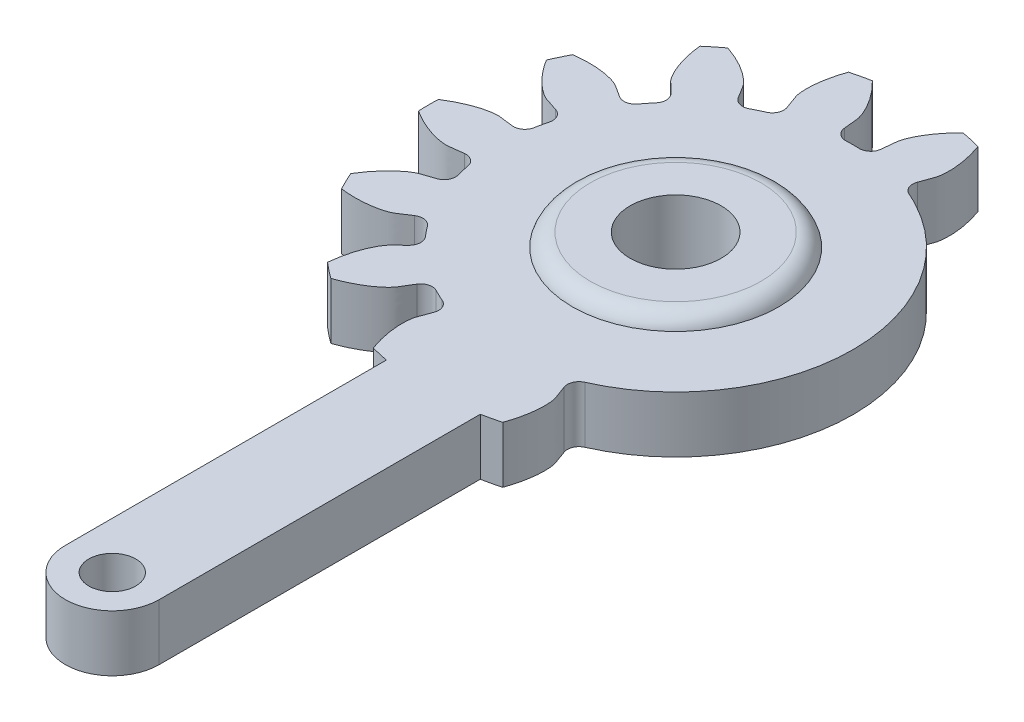
SolidWorks part; units mm, degrees
ref_plane "Front Plane" through (0, 0, 0) normal (0, 0, 1) x (1, 0, 0)
ref_plane "Top Plane" through (0, 0, 0) normal (0, 1, 0) x (1, 0, 0)
ref_plane "Right Plane" through (0, 0, 0) normal (1, 0, 0) x (0, 0, -1)
ref_plane "Plane1" through (0, 0, 0) normal (0, -1, 0) x (1, 0, 0)
sketch "Sketch1" plane through (0, 0, 0) normal (0, -1, 0) x (1, 0, 0)
  line L0 (9, 29) -> (9, 11.9029)
  line L1 (14, 11.9029) -> (14, 29)
  arc A0 (9, 11.9029) -> (14, 11.9029) centre (11.5, -1) ccw
  arc A1 (14, 29) -> (9, 29) centre (11.5, 29) ccw
extrude "Boss-Extrude1" add sketch "Sketch1" against normal blind 3
sketch "Sketch2" plane through (0, 3, 0) normal (0, 1, 0) x (-1, 0, 0)
  arc A0 (-8.2696, 7.8769) -> (-6.6141, 7.0847) centre (-11.5, -1) cw
  arc A1 (-3.7528, 9.6168) -> (-8.093, 11.6936) centre (-11.5, -1) ccw
  spline S0 degree 3 poles (-8.2696, 7.8769) (-8.0543, 8.4631) (-7.8019, 9.15) (-7.7905, 9.2032) (-7.7728, 9.277) (-7.7573, 9.3673) (-7.742, 9.4889) (-7.7311, 9.6368) (-7.7269, 9.8125) (-7.7321, 10.0151) (-7.7496, 10.2441) (-7.7818, 10.4988) (-7.8315, 10.7782) (-7.9014, 11.0811) (-7.9873, 11.388) (-8.059, 11.5963) (-8.093, 11.6936) knots 0 0 0 0 0.172234 0.201817 0.240008 0.285196 0.336434 0.39308 0.454661 0.520809 0.59123 0.665677 0.743945 0.825855 0.911253 0.985951 0.985951 0.985951 0.985951
  spline S1 degree 3 poles (-6.6141, 7.0847) (-6.2927, 7.6202) (-5.9162, 8.2476) (-5.8819, 8.2899) (-5.8356, 8.35) (-5.7749, 8.4187) (-5.6899, 8.5069) (-5.5815, 8.6082) (-5.4474, 8.7217) (-5.2863, 8.8447) (-5.097, 8.9749) (-4.8784, 9.1095) (-4.6298, 9.2462) (-4.35, 9.3818) (-4.0571, 9.5074) (-3.8499, 9.5822) (-3.7528, 9.6168) knots 0 0 0 0 0.172234 0.201817 0.240008 0.285196 0.336434 0.39308 0.454661 0.520809 0.59123 0.665677 0.743945 0.825855 0.911253 0.985951 0.985951 0.985951 0.985951
extrude "Cut-Extrude1" cut sketch "Sketch2" against normal through all
sketch "Sketch3" plane through (0, 3, 0) normal (0, 1, 0) x (-1, 0, 0)
  arc A0 (-4.738, 5.5962) -> (-3.5901, 4.1642) centre (-11.5, -1) cw
  arc A1 (0.0864, 5.204) -> (-2.9229, 8.9583) centre (-11.5, -1) ccw
  spline S0 degree 3 poles (-4.738, 5.5962) (-4.2896, 6.0309) (-3.7642, 6.5403) (-3.7309, 6.5832) (-3.6829, 6.642) (-3.6298, 6.7167) (-3.5632, 6.8196) (-3.4892, 6.9482) (-3.4091, 7.1046) (-3.326, 7.2894) (-3.2423, 7.5034) (-3.1609, 7.7468) (-3.0844, 8.0201) (-3.0159, 8.3234) (-2.9602, 8.6371) (-2.9345, 8.8558) (-2.9229, 8.9583) knots 0 0 0 0 0.172234 0.201817 0.240008 0.285196 0.336434 0.39308 0.454661 0.520809 0.59123 0.665677 0.743945 0.825855 0.911253 0.985951 0.985951 0.985951 0.985951
  spline S1 degree 3 poles (-3.5901, 4.1642) (-3.0683, 4.5072) (-2.4567, 4.9091) (-2.4076, 4.9323) (-2.3397, 4.9664) (-2.2553, 5.0019) (-2.1404, 5.0445) (-1.9988, 5.0888) (-1.8287, 5.1329) (-1.6302, 5.1738) (-1.4032, 5.2089) (-1.1478, 5.2354) (-0.8645, 5.2506) (-0.5536, 5.2514) (-0.2352, 5.2375) (-0.0161, 5.215) (0.0864, 5.204) knots 0 0 0 0 0.172234 0.201817 0.240008 0.285196 0.336434 0.39308 0.454661 0.520809 0.59123 0.665677 0.743945 0.825855 0.911253 0.985951 0.985951 0.985951 0.985951
extrude "Cut-Extrude2" cut sketch "Sketch3" against normal through all
sketch "Sketch4" plane through (0, 3, 0) normal (0, 1, 0) x (-1, 0, 0)
  arc A0 (-2.5456, 2.0091) -> (-2.1328, 0.2208) centre (-11.5, -1) cw
  arc A1 (1.6308, -0.4375) -> (0.5485, 4.2506) centre (-11.5, -1) ccw
  spline S0 degree 3 poles (-2.5456, 2.0091) (-1.9531, 2.2062) (-1.2587, 2.4371) (-1.21, 2.4614) (-1.1412, 2.4935) (-1.061, 2.5378) (-0.9564, 2.6016) (-0.8339, 2.6853) (-0.6939, 2.7915) (-0.5388, 2.922) (-0.3706, 3.0784) (-0.1916, 3.2624) (-0.0041, 3.4754) (0.1891, 3.719) (0.3755, 3.9775) (0.4936, 4.1634) (0.5485, 4.2506) knots 0 0 0 0 0.172234 0.201817 0.240008 0.285196 0.336434 0.39308 0.454661 0.520809 0.59123 0.665677 0.743945 0.825855 0.911253 0.985951 0.985951 0.985951 0.985951
  spline S1 degree 3 poles (-2.1328, 0.2208) (-1.5138, 0.3034) (-0.7884, 0.4002) (-0.734, 0.3998) (-0.6582, 0.401) (-0.5666, 0.3964) (-0.4446, 0.3849) (-0.2979, 0.3634) (-0.1255, 0.3293) (0.0711, 0.28) (0.2909, 0.2132) (0.5324, 0.1262) (0.7943, 0.017) (1.0748, -0.1172) (1.3556, -0.2678) (1.5432, -0.3832) (1.6308, -0.4375) knots 0 0 0 0 0.172234 0.201817 0.240008 0.285196 0.336434 0.39308 0.454661 0.520809 0.59123 0.665677 0.743945 0.825855 0.911253 0.985951 0.985951 0.985951 0.985951
extrude "Cut-Extrude3" cut sketch "Sketch4" against normal through all
sketch "Sketch5" plane through (0, 3, 0) normal (0, 1, 0) x (-1, 0, 0)
  arc A0 (-2.1268, -2.1741) -> (-2.5307, -3.9644) centre (-11.5, -1) cw
  arc A1 (0.5745, -6.1905) -> (1.6335, -1.497) centre (-11.5, -1) ccw
  spline S0 degree 3 poles (-2.1268, -2.1741) (-1.5074, -2.2536) (-0.7816, -2.3468) (-0.7272, -2.3461) (-0.6513, -2.347) (-0.5598, -2.3419) (-0.4379, -2.3298) (-0.2912, -2.3075) (-0.119, -2.2725) (0.0773, -2.2223) (0.2968, -2.1544) (0.5379, -2.0662) (0.7992, -1.9557) (1.079, -1.8201) (1.3591, -1.668) (1.5461, -1.5518) (1.6335, -1.497) knots 0 0 0 0 0.172234 0.201817 0.240008 0.285196 0.336434 0.39308 0.454661 0.520809 0.59123 0.665677 0.743945 0.825855 0.911253 0.985951 0.985951 0.985951 0.985951
  spline S1 degree 3 poles (-2.5307, -3.9644) (-1.9372, -4.1585) (-1.2417, -4.386) (-1.1929, -4.41) (-1.1239, -4.4418) (-1.0435, -4.4857) (-0.9386, -4.549) (-0.8157, -4.6321) (-0.6752, -4.7376) (-0.5194, -4.8672) (-0.3504, -5.0228) (-0.1705, -5.206) (0.018, -5.418) (0.2125, -5.6606) (0.4002, -5.9182) (0.5192, -6.1035) (0.5745, -6.1905) knots 0 0 0 0 0.172234 0.201817 0.240008 0.285196 0.336434 0.39308 0.454661 0.520809 0.59123 0.665677 0.743945 0.825855 0.911253 0.985951 0.985951 0.985951 0.985951
extrude "Cut-Extrude4" cut sketch "Sketch5" against normal through all
sketch "Sketch6" plane through (0, 3, 0) normal (0, 1, 0) x (-1, 0, 0)
  arc A0 (-3.5645, -6.1247) -> (-4.7052, -7.5624) centre (-11.5, -1) cw
  arc A1 (-2.8733, -10.9154) -> (0.1172, -7.1462) centre (-11.5, -1) ccw
  spline S0 degree 3 poles (-3.5645, -6.1247) (-3.0409, -6.4651) (-2.4274, -6.8639) (-2.3781, -6.8869) (-2.3101, -6.9206) (-2.2254, -6.9558) (-2.1103, -6.9978) (-1.9685, -7.0413) (-1.7982, -7.0846) (-1.5995, -7.1245) (-1.3723, -7.1585) (-1.1168, -7.1837) (-0.8334, -7.1975) (-0.5225, -7.1967) (-0.2042, -7.1812) (0.0147, -7.1576) (0.1172, -7.1462) knots 0 0 0 0 0.172234 0.201817 0.240008 0.285196 0.336434 0.39308 0.454661 0.520809 0.59123 0.665677 0.743945 0.825855 0.911253 0.985951 0.985951 0.985951 0.985951
  spline S1 degree 3 poles (-4.7052, -7.5624) (-4.2546, -7.9949) (-3.7267, -8.5016) (-3.6931, -8.5444) (-3.6448, -8.603) (-3.5914, -8.6774) (-3.5243, -8.7799) (-3.4497, -8.9081) (-3.3688, -9.0642) (-3.2848, -9.2486) (-3.2, -9.4621) (-3.1174, -9.7051) (-3.0395, -9.978) (-2.9696, -10.2809) (-2.9122, -10.5944) (-2.8854, -10.813) (-2.8733, -10.9154) knots 0 0 0 0 0.172234 0.201817 0.240008 0.285196 0.336434 0.39308 0.454661 0.520809 0.59123 0.665677 0.743945 0.825855 0.911253 0.985951 0.985951 0.985951 0.985951
extrude "Cut-Extrude5" cut sketch "Sketch6" against normal through all
sketch "Sketch7" plane through (0, 3, 0) normal (0, 1, 0) x (-1, 0, 0)
  arc A0 (-6.5739, -9.0603) -> (-8.2254, -9.8607) centre (-11.5, -1) cw
  arc A1 (-8.0298, -13.6764) -> (-3.7, -11.578) centre (-11.5, -1) ccw
  spline S0 degree 3 poles (-6.5739, -9.0603) (-6.2498, -9.5941) (-5.8701, -10.2197) (-5.8357, -10.2618) (-5.789, -10.3217) (-5.728, -10.39) (-5.6426, -10.4778) (-5.5337, -10.5786) (-5.399, -10.6914) (-5.2373, -10.8136) (-5.0473, -10.9428) (-4.8281, -11.0764) (-4.5787, -11.2118) (-4.2983, -11.346) (-4.0048, -11.4702) (-3.7973, -11.5439) (-3.7, -11.578) knots 0 0 0 0 0.172234 0.201817 0.240008 0.285196 0.336434 0.39308 0.454661 0.520809 0.59123 0.665677 0.743945 0.825855 0.911253 0.985951 0.985951 0.985951 0.985951
  spline S1 degree 3 poles (-8.2254, -9.8607) (-8.0071, -10.4458) (-7.7514, -11.1314) (-7.7397, -11.1845) (-7.7215, -11.2583) (-7.7057, -11.3485) (-7.6897, -11.47) (-7.6781, -11.6179) (-7.673, -11.7935) (-7.6773, -11.9962) (-7.6935, -12.2253) (-7.7245, -12.4801) (-7.7728, -12.7597) (-7.8412, -13.063) (-7.9256, -13.3704) (-7.9963, -13.5789) (-8.0298, -13.6764) knots 0 0 0 0 0.172234 0.201817 0.240008 0.285196 0.336434 0.39308 0.454661 0.520809 0.59123 0.665677 0.743945 0.825855 0.911253 0.985951 0.985951 0.985951 0.985951
extrude "Cut-Extrude6" cut sketch "Sketch7" against normal through all
sketch "Sketch8" plane through (0, 3, 0) normal (0, 1, 0) x (-1, 0, 0)
  arc A0 (-10.5589, -10.3994) -> (-12.3942, -10.404) centre (-11.5, -1) cw
  arc A1 (-13.8735, -13.9268) -> (-9.0621, -13.9148) centre (-11.5, -1) ccw
  spline S0 degree 3 poles (-10.5589, -10.3994) (-10.4986, -11.021) (-10.4279, -11.7494) (-10.4152, -11.8022) (-10.3991, -11.8764) (-10.3738, -11.9645) (-10.3349, -12.0807) (-10.2805, -12.2187) (-10.2081, -12.3788) (-10.1155, -12.5591) (-10.0004, -12.7579) (-9.8608, -12.9733) (-9.6949, -13.2035) (-9.5004, -13.4461) (-9.2899, -13.6853) (-9.1349, -13.8418) (-9.0621, -13.9148) knots 0 0 0 0 0.172234 0.201817 0.240008 0.285196 0.336434 0.39308 0.454661 0.520809 0.59123 0.665677 0.743945 0.825855 0.911253 0.985951 0.985951 0.985951 0.985951
  spline S1 degree 3 poles (-12.3942, -10.404) (-12.4514, -11.0259) (-12.5184, -11.7546) (-12.531, -11.8075) (-12.5466, -11.8818) (-12.5715, -11.97) (-12.6098, -12.0864) (-12.6635, -12.2246) (-12.7351, -12.3851) (-12.8269, -12.5658) (-12.941, -12.7652) (-13.0795, -12.9814) (-13.2442, -13.2123) (-13.4375, -13.4559) (-13.6468, -13.6962) (-13.801, -13.8534) (-13.8735, -13.9268) knots 0 0 0 0 0.172234 0.201817 0.240008 0.285196 0.336434 0.39308 0.454661 0.520809 0.59123 0.665677 0.743945 0.825855 0.911253 0.985951 0.985951 0.985951 0.985951
extrude "Cut-Extrude7" cut sketch "Sketch8" against normal through all
sketch "Sketch9" plane through (0, 3, 0) normal (0, 1, 0) x (-1, 0, 0)
  arc A0 (-14.7304, -9.8769) -> (-16.3859, -9.0847) centre (-11.5, -1) cw
  arc A1 (-19.2472, -11.6168) -> (-14.907, -13.6936) centre (-11.5, -1) ccw
  spline S0 degree 3 poles (-14.7304, -9.8769) (-14.9457, -10.4631) (-15.1981, -11.15) (-15.2095, -11.2032) (-15.2272, -11.277) (-15.2427, -11.3673) (-15.258, -11.4889) (-15.2689, -11.6368) (-15.2731, -11.8125) (-15.2679, -12.0151) (-15.2504, -12.2441) (-15.2182, -12.4988) (-15.1685, -12.7782) (-15.0986, -13.0811) (-15.0127, -13.388) (-14.941, -13.5963) (-14.907, -13.6936) knots 0 0 0 0 0.172234 0.201817 0.240008 0.285196 0.336434 0.39308 0.454661 0.520809 0.59123 0.665677 0.743945 0.825855 0.911253 0.985951 0.985951 0.985951 0.985951
  spline S1 degree 3 poles (-16.3859, -9.0847) (-16.7073, -9.6202) (-17.0838, -10.2476) (-17.1181, -10.2899) (-17.1644, -10.35) (-17.2251, -10.4187) (-17.3101, -10.5069) (-17.4185, -10.6082) (-17.5526, -10.7217) (-17.7137, -10.8447) (-17.903, -10.9749) (-18.1216, -11.1095) (-18.3702, -11.2462) (-18.65, -11.3818) (-18.9429, -11.5074) (-19.1501, -11.5822) (-19.2472, -11.6168) knots 0 0 0 0 0.172234 0.201817 0.240008 0.285196 0.336434 0.39308 0.454661 0.520809 0.59123 0.665677 0.743945 0.825855 0.911253 0.985951 0.985951 0.985951 0.985951
extrude "Cut-Extrude8" cut sketch "Sketch9" against normal through all
sketch "Sketch10" plane through (0, 3, 0) normal (0, 1, 0) x (-1, 0, 0)
  arc A0 (-18.262, -7.5962) -> (-19.4099, -6.1642) centre (-11.5, -1) cw
  arc A1 (-23.0864, -7.204) -> (-20.0771, -10.9583) centre (-11.5, -1) ccw
  spline S0 degree 3 poles (-18.262, -7.5962) (-18.7104, -8.0309) (-19.2358, -8.5403) (-19.2691, -8.5832) (-19.3171, -8.642) (-19.3702, -8.7167) (-19.4368, -8.8196) (-19.5108, -8.9482) (-19.5909, -9.1046) (-19.674, -9.2894) (-19.7577, -9.5034) (-19.8391, -9.7468) (-19.9156, -10.0201) (-19.9841, -10.3234) (-20.0398, -10.6371) (-20.0655, -10.8558) (-20.0771, -10.9583) knots 0 0 0 0 0.172234 0.201817 0.240008 0.285196 0.336434 0.39308 0.454661 0.520809 0.59123 0.665677 0.743945 0.825855 0.911253 0.985951 0.985951 0.985951 0.985951
  spline S1 degree 3 poles (-19.4099, -6.1642) (-19.9317, -6.5072) (-20.5433, -6.9091) (-20.5924, -6.9323) (-20.6603, -6.9664) (-20.7447, -7.0019) (-20.8596, -7.0445) (-21.0012, -7.0888) (-21.1713, -7.1329) (-21.3698, -7.1738) (-21.5968, -7.2089) (-21.8522, -7.2354) (-22.1355, -7.2506) (-22.4464, -7.2514) (-22.7648, -7.2375) (-22.9839, -7.215) (-23.0864, -7.204) knots 0 0 0 0 0.172234 0.201817 0.240008 0.285196 0.336434 0.39308 0.454661 0.520809 0.59123 0.665677 0.743945 0.825855 0.911253 0.985951 0.985951 0.985951 0.985951
extrude "Cut-Extrude9" cut sketch "Sketch10" against normal through all
sketch "Sketch11" plane through (0, 3, 0) normal (0, 1, 0) x (-1, 0, 0)
  arc A0 (-20.4544, -4.0091) -> (-20.8672, -2.2208) centre (-11.5, -1) cw
  arc A1 (-24.6308, -1.5625) -> (-23.5485, -6.2506) centre (-11.5, -1) ccw
  spline S0 degree 3 poles (-20.4544, -4.0091) (-21.0469, -4.2062) (-21.7413, -4.4371) (-21.79, -4.4614) (-21.8588, -4.4935) (-21.939, -4.5378) (-22.0436, -4.6016) (-22.1661, -4.6853) (-22.3061, -4.7915) (-22.4612, -4.922) (-22.6294, -5.0784) (-22.8084, -5.2624) (-22.9959, -5.4754) (-23.1891, -5.719) (-23.3755, -5.9775) (-23.4936, -6.1634) (-23.5485, -6.2506) knots 0 0 0 0 0.172234 0.201817 0.240008 0.285196 0.336434 0.39308 0.454661 0.520809 0.59123 0.665677 0.743945 0.825855 0.911253 0.985951 0.985951 0.985951 0.985951
  spline S1 degree 3 poles (-20.8672, -2.2208) (-21.4862, -2.3034) (-22.2116, -2.4002) (-22.266, -2.3998) (-22.3418, -2.401) (-22.4334, -2.3964) (-22.5554, -2.3849) (-22.7021, -2.3634) (-22.8745, -2.3293) (-23.0711, -2.28) (-23.2909, -2.2132) (-23.5324, -2.1262) (-23.7943, -2.017) (-24.0748, -1.8828) (-24.3556, -1.7322) (-24.5432, -1.6168) (-24.6308, -1.5625) knots 0 0 0 0 0.172234 0.201817 0.240008 0.285196 0.336434 0.39308 0.454661 0.520809 0.59123 0.665677 0.743945 0.825855 0.911253 0.985951 0.985951 0.985951 0.985951
extrude "Cut-Extrude10" cut sketch "Sketch11" against normal through all
sketch "Sketch12" plane through (0, 3, 0) normal (0, 1, 0) x (-1, 0, 0)
  arc A0 (-20.8732, 0.1741) -> (-20.4693, 1.9644) centre (-11.5, -1) cw
  arc A1 (-23.5745, 4.1905) -> (-24.6335, -0.503) centre (-11.5, -1) ccw
  spline S0 degree 3 poles (-20.8732, 0.1741) (-21.4926, 0.2536) (-22.2184, 0.3468) (-22.2728, 0.3461) (-22.3487, 0.347) (-22.4402, 0.3419) (-22.5621, 0.3298) (-22.7088, 0.3075) (-22.881, 0.2725) (-23.0773, 0.2223) (-23.2968, 0.1544) (-23.5379, 0.0662) (-23.7992, -0.0443) (-24.079, -0.1799) (-24.3591, -0.332) (-24.5461, -0.4482) (-24.6335, -0.503) knots 0 0 0 0 0.172234 0.201817 0.240008 0.285196 0.336434 0.39308 0.454661 0.520809 0.59123 0.665677 0.743945 0.825855 0.911253 0.985951 0.985951 0.985951 0.985951
  spline S1 degree 3 poles (-20.4693, 1.9644) (-21.0628, 2.1585) (-21.7583, 2.386) (-21.8071, 2.41) (-21.8761, 2.4418) (-21.9565, 2.4857) (-22.0614, 2.549) (-22.1843, 2.6321) (-22.3248, 2.7376) (-22.4806, 2.8672) (-22.6496, 3.0228) (-22.8295, 3.206) (-23.018, 3.418) (-23.2125, 3.6606) (-23.4002, 3.9182) (-23.5192, 4.1035) (-23.5745, 4.1905) knots 0 0 0 0 0.172234 0.201817 0.240008 0.285196 0.336434 0.39308 0.454661 0.520809 0.59123 0.665677 0.743945 0.825855 0.911253 0.985951 0.985951 0.985951 0.985951
extrude "Cut-Extrude11" cut sketch "Sketch12" against normal through all
sketch "Sketch13" plane through (0, 3, 0) normal (0, 1, 0) x (-1, 0, 0)
  arc A0 (-19.4355, 4.1247) -> (-18.2948, 5.5624) centre (-11.5, -1) cw
  arc A1 (-20.1267, 8.9154) -> (-23.1172, 5.1462) centre (-11.5, -1) ccw
  spline S0 degree 3 poles (-19.4355, 4.1247) (-19.9591, 4.4651) (-20.5726, 4.8639) (-20.6219, 4.8869) (-20.6899, 4.9206) (-20.7746, 4.9558) (-20.8897, 4.9978) (-21.0315, 5.0413) (-21.2018, 5.0846) (-21.4005, 5.1245) (-21.6277, 5.1585) (-21.8832, 5.1837) (-22.1666, 5.1975) (-22.4775, 5.1967) (-22.7958, 5.1812) (-23.0147, 5.1576) (-23.1172, 5.1462) knots 0 0 0 0 0.172234 0.201817 0.240008 0.285196 0.336434 0.39308 0.454661 0.520809 0.59123 0.665677 0.743945 0.825855 0.911253 0.985951 0.985951 0.985951 0.985951
  spline S1 degree 3 poles (-18.2948, 5.5624) (-18.7454, 5.9949) (-19.2733, 6.5016) (-19.3069, 6.5444) (-19.3552, 6.603) (-19.4086, 6.6774) (-19.4757, 6.7799) (-19.5503, 6.9081) (-19.6312, 7.0642) (-19.7152, 7.2486) (-19.8, 7.4621) (-19.8826, 7.7051) (-19.9605, 7.978) (-20.0304, 8.2809) (-20.0878, 8.5944) (-20.1146, 8.813) (-20.1267, 8.9154) knots 0 0 0 0 0.172234 0.201817 0.240008 0.285196 0.336434 0.39308 0.454661 0.520809 0.59123 0.665677 0.743945 0.825855 0.911253 0.985951 0.985951 0.985951 0.985951
extrude "Cut-Extrude12" cut sketch "Sketch13" against normal through all
sketch "Sketch14" plane through (0, 3, 0) normal (0, 1, 0) x (-1, 0, 0)
  arc A0 (-16.4261, 7.0603) -> (-14.7746, 7.8607) centre (-11.5, -1) cw
  arc A1 (-14.9702, 11.6764) -> (-19.3, 9.578) centre (-11.5, -1) ccw
  spline S0 degree 3 poles (-16.4261, 7.0603) (-16.7502, 7.5941) (-17.1299, 8.2197) (-17.1643, 8.2618) (-17.211, 8.3217) (-17.272, 8.39) (-17.3574, 8.4778) (-17.4663, 8.5786) (-17.601, 8.6914) (-17.7627, 8.8136) (-17.9527, 8.9428) (-18.1719, 9.0764) (-18.4213, 9.2118) (-18.7017, 9.346) (-18.9952, 9.4702) (-19.2027, 9.5439) (-19.3, 9.578) knots 0 0 0 0 0.172234 0.201817 0.240008 0.285196 0.336434 0.39308 0.454661 0.520809 0.59123 0.665677 0.743945 0.825855 0.911253 0.985951 0.985951 0.985951 0.985951
  spline S1 degree 3 poles (-14.7746, 7.8607) (-14.9929, 8.4458) (-15.2486, 9.1314) (-15.2603, 9.1845) (-15.2785, 9.2583) (-15.2943, 9.3485) (-15.3103, 9.47) (-15.3219, 9.6179) (-15.327, 9.7935) (-15.3227, 9.9962) (-15.3065, 10.2253) (-15.2755, 10.4801) (-15.2272, 10.7597) (-15.1588, 11.063) (-15.0744, 11.3704) (-15.0037, 11.5789) (-14.9702, 11.6764) knots 0 0 0 0 0.172234 0.201817 0.240008 0.285196 0.336434 0.39308 0.454661 0.520809 0.59123 0.665677 0.743945 0.825855 0.911253 0.985951 0.985951 0.985951 0.985951
extrude "Cut-Extrude13" cut sketch "Sketch14" against normal through all
ref_plane "Plane2" through (0, 0, -1) normal (0, 0, 1) x (1, 0, 0)
sketch "Sketch15" plane through (0, 0, -1) normal (0, 0, 1) x (1, 0, 0)
  line L0 (17, 3.7) -> (11.5, 3.7)
  line L1 (11.5, 3.7) -> (11.5, 2.5)
  line L2 (11.5, 2.5) -> (17, 2.5)
  line L3 (17, 2.5) -> (17, 3.7)
  line L4 (11.5, 3.7) -> (11.5, 2.5) construction
  dimension "D1" = 1.2
revolve "Revolve1" add sketch "Sketch15" angle 360 about L4 reverse direction yes
hole_wizard "M4 Clearance Hole1" positions "Sketch17" profile "Sketch16" hole size "M4" standard "ANSI Metric" end condition through all
sketch "Sketch17" plane through (0, 3.7, 0) normal (0, 1, 0) x (1, 0, 0)
  point P0 (11.5, 1)
sketch "Sketch16" plane through (11.5, 3.7, -1) normal (1, 0, 0) x (0, 0, 1)
  line L0 (0, 0) -> (0, 3.7)
  line L1 (0, 3.7) -> (2.425, 3.7)
  line L2 (2.425, 3.7) -> (2.425, 0)
  line L5 (2.425, 0) -> (0, 0)
  line L11 (0, -6.35) -> (0, 107.95) construction
  dimension "Thru Hole Dia." = 4.85
  dimension "Thru Hole Depth" = 3.7
hole_wizard "Ø2.0 (2) Diameter Hole1" positions "Sketch19" profile "Sketch18" hole size "Ø2.0" standard "ANSI Metric"
sketch "Sketch19" plane through (0, 0, 0) normal (0, -1, 0) x (-1, 0, 0)
  point P0 (-11.5, -29)
sketch "Sketch18" plane through (11.5, 0, 29) normal (1, 0, 0) x (0, 0, -1)
  line L0 (0, 0) -> (0, 3.7)
  line L1 (0, 3.7) -> (1, 3.7)
  line L2 (1, 3.7) -> (1, 0)
  line L5 (1, 0) -> (0, 0)
  line L11 (0, -6.35) -> (0, 107.95) construction
  dimension "Thru Hole Dia." = 2
  dimension "Thru Hole Depth" = 3.7
fillet "Fillet1" radius 0.6118 26 edges at (18.262, 1.5, -7.5962) (3.5645, 1.5, -6.1247) (10.5589, 1.5, -10.3994) (2.5456, 1.5, 2.0091) (20.4544, 1.5, -4.0091) (3.5901, 1.5, 4.1642) (14.7304, 1.5, -9.8769) (4.738, 1.5, 5.5962) (6.5739, 1.5, -9.0603) (6.6141, 1.5, 7.0847) (2.1268, 1.5, -2.1741) (8.2696, 1.5, 7.8769) (19.4099, 1.5, -6.1642) (14.7746, 1.5, 7.8607) (16.3859, 1.5, -9.0847) (16.4261, 1.5, 7.0603) (12.3942, 1.5, -10.404) (18.2948, 1.5, 5.5624) (8.2254, 1.5, -9.8607) (19.4355, 1.5, 4.1247) (4.7052, 1.5, -7.5624) (20.4693, 1.5, 1.9644) (2.5307, 1.5, -3.9644) (20.8732, 1.5, 0.1741) (2.1328, 1.5, 0.2208) (20.8672, 1.5, -2.2208) tangent propagation no
sketch "Sketch20" plane through (0, 3, 0) normal (0, 1, 0) x (1, 0, 0)
  line L0 (15.9254, -7.3457) -> (15.9254, -11.6853)
  line L1 (15.9254, -11.6853) -> (26.923, -11.6853)
  line L2 (26.923, -11.6853) -> (26.923, 14.2384)
  line L3 (15.9254, 9.3457) -> (15.9254, 14.2384)
  line L4 (15.9254, 14.2384) -> (26.923, 14.2384)
  arc A0 (15.9254, -7.3457) -> (15.9254, 9.3457) centre (11.5, 1) ccw
extrude "Cut-Extrude14" cut sketch "Sketch20" against normal blind 10
sketch "Sketch21" plane through (0, 3, 0) normal (0, 1, 0) x (1, 0, 0)
  circle A0 centre (11.5, -29) radius 1.25
  dimension "D1" = 2.5
extrude "Cut-Extrude15" cut sketch "Sketch21" against normal through all
fillet "Fillet2" radius 1 1 edges at (11.5, 3.7, -6.5)
